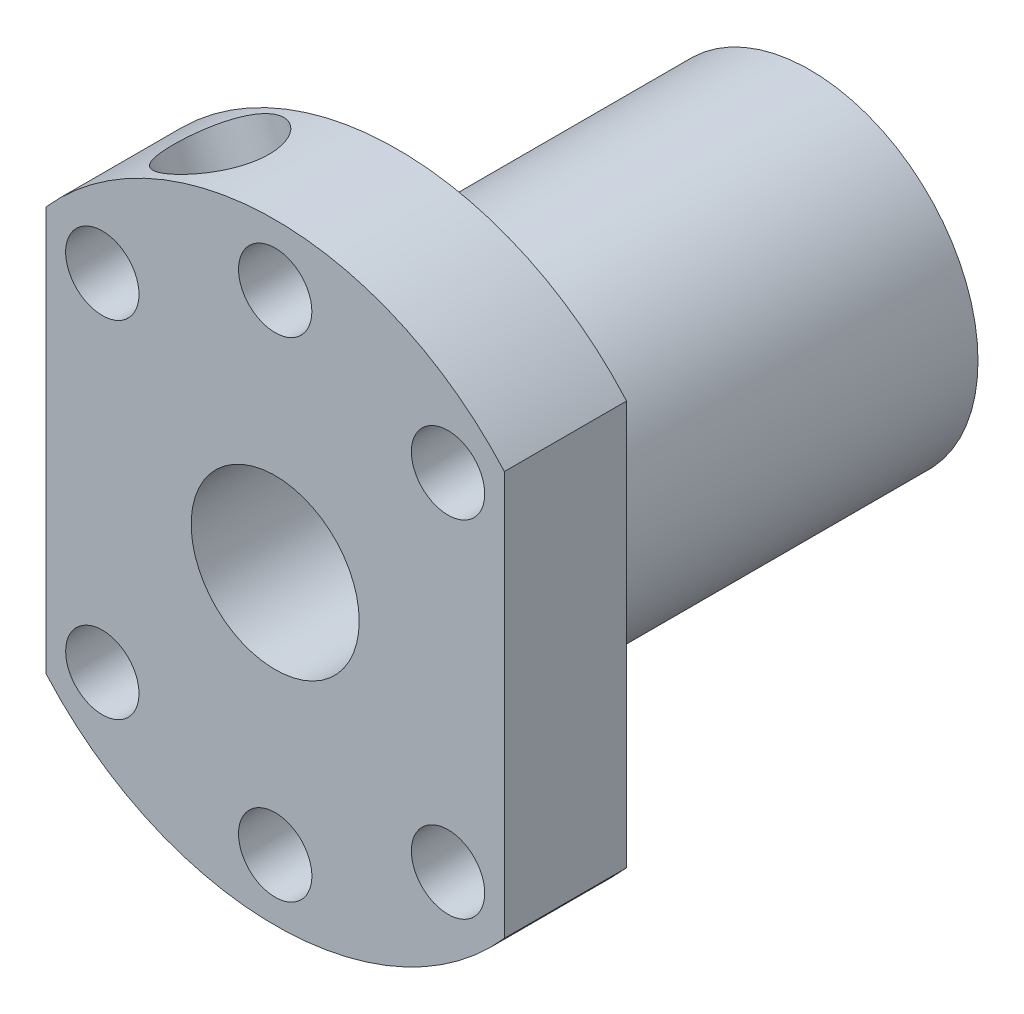
SolidWorks part; units mm, degrees
ref_plane "Front Plane" through (0, 0, 0) normal (0, 0, 1) x (1, 0, 0)
ref_plane "Top Plane" through (0, 0, 0) normal (0, 1, 0) x (1, 0, 0)
ref_plane "Right Plane" through (0, 0, 0) normal (1, 0, 0) x (0, 0, -1)
sketch "Sketch1" plane through (0, 0, 0) normal (0, 0, 1) x (1, 0, 0)
  line L0 (0, -20) -> (0, 20) construction
  line L1 (0, 0) -> (-15, 0) construction
  line L2 (-15, 13.2288) -> (-15, -13.2288)
  line L3 (15, 13.2288) -> (15, -13.2288)
  line L4 (0, 0) -> (-11.3137, 11.3137) construction
  line L5 (0, 0) -> (-7.6537, 18.4776) construction
  circle A0 centre (0, 0) radius 5.5
  circle A1 centre (-11.3137, 11.3137) radius 2.4
  circle A2 centre (0, 16) radius 2.4
  arc A5 (0, 16) -> (-11.3137, 11.3137) centre (0, 0) ccw construction
  arc A6 (15, 13.2288) -> (-15, 13.2288) centre (0, 0) ccw
  circle A8 centre (11.3137, 11.3137) radius 2.4
  circle A9 centre (11.3137, -11.3137) radius 2.4
  arc A10 (15, -13.2288) -> (-15, -13.2288) centre (0, 0) cw
  circle A11 centre (0, -16) radius 2.4
  circle A12 centre (-11.3137, -11.3137) radius 2.4
  point P12 (0, 0)
  point P29 (15, 0)
  dimension "D2" = 32
  dimension "D3" = 4.8
  dimension "D1" = 40
  dimension "D7" = 11
  dimension "D4" = 45
  dimension "D5" = 30
  dimension "D6" = 22.5
extrude "Boss-Extrude1" add sketch "Sketch1" against normal mid plane 8
sketch "Sketch2" plane through (0, 0, -4) normal (0, 0, -1) x (-1, 0, 0)
  circle A0 centre (0, 0) radius 11
  circle A1 centre (0, 0) radius 5.5 construction
  circle A2 centre (0, 0) radius 5.5
  dimension "D1" = 22
extrude "Boss-Extrude2" add sketch "Sketch2" along normal offset from surface (27 mm away) 35 up to face at (-13.7137, -11.3137, 4)
hole_wizard "M8x1.25 Tapped Hole1" positions "3DSketch3" profile "Sketch4" tap size "M8x1.25" standard "ANSI Metric"
sketch3d "3DSketch3"
  point P0 (-7.6537, 18.4776, 0)
  point P3 (-7.6537, 18.4776, 0)
  point P5 (-7.6537, 18.4776, 0)
  point P8 (-8.0765, 18.2967, 1.8666)
  point P9 (-7.6537, 18.4776, 0)
sketch "Sketch4" plane through (-7.6537, 18.4776, 0) normal (0, 0, 1) x (-0.9239, -0.3827, 0)
  line L0 (0, 0) -> (0, 10.0429)
  line L1 (0, 10.0429) -> (3.4, 8)
  line L2 (3.4, 8) -> (3.4, 0)
  line L5 (3.4, 0) -> (0, 0)
  line L10 (0, 10.0429) -> (-3.4, 8) construction
  line L11 (0, -6.35) -> (0, 107.95) construction
  dimension "Tap Drill Dia." = 6.8
  dimension "Tap Drill Depth" = 8
  dimension "Drill Angle" = 118
cosmetic thread "Hole Thread3" parameters "D1"=8, "D2"=8
